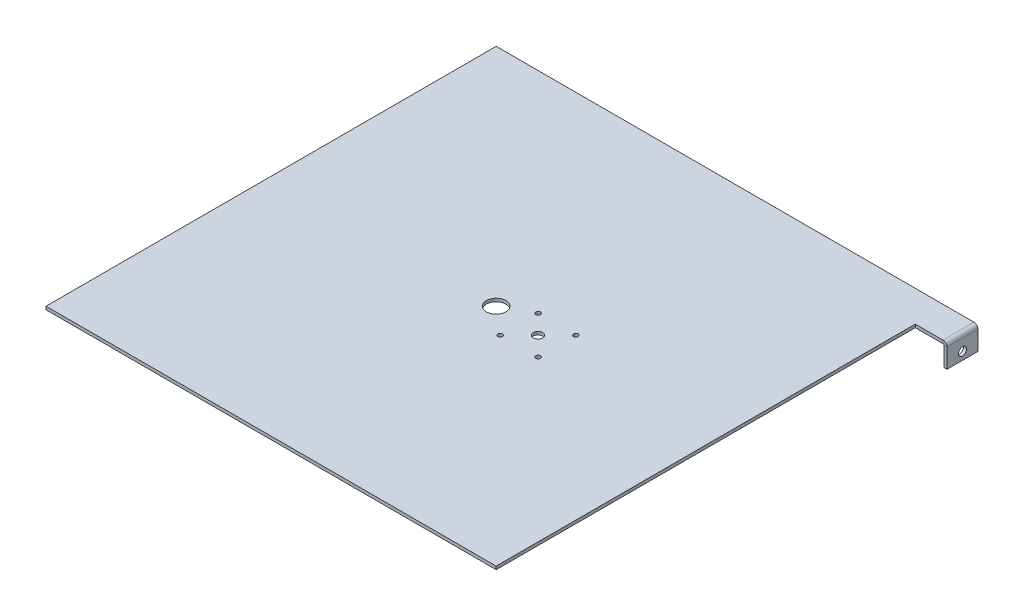
SolidWorks part; units mm, degrees
note: The reader was unsure of these and kept them because the rebuilt part matched: flange length of "Edge-Flange1".
ref_plane "Front Plane" through (0, 0, 0) normal (0, 0, 1) x (1, 0, 0)
ref_plane "Top Plane" through (0, 0, 0) normal (0, 1, 0) x (1, 0, 0)
ref_plane "Right Plane" through (0, 0, 0) normal (1, 0, 0) x (0, 0, -1)
sketch "Sketch1" plane through (0, 0, 0) normal (0, 1, 0) x (1, 0, 0)
  line L1 (0, 0) -> (368.3, 0)
  line L2 (0, 0) -> (0, 368.3)
  line L3 (0, 368.3) -> (368.3, 368.3)
  line L4 (368.3, 0) -> (368.3, 342.9)
  line L5 (368.3, 368.3) -> (394.208, 368.3)
  line L7 (368.3, 342.9) -> (394.208, 342.9)
  line L8 (394.208, 368.3) -> (394.208, 342.9)
  dimension "D1" = 368.3
  dimension "D2" = 368.3
  dimension "D3" = 25.908
  dimension "D4" = 25.4
base flange "Base-Flange1" sketch "Sketch1" thickness 2.54 reverse thickness direction no parameters "D1"=0.7366
sketch "Sketch6" plane through (0, 0, 0) normal (0, 1, 0) x (1, 0, 0)
  circle A0 centre (221.844, 180.7376) radius 3.81
  circle A1 centre (237.338, 165.2436) radius 1.905
  circle A2 centre (237.338, 196.2316) radius 1.905
  circle A3 centre (206.35, 196.2316) radius 1.905
  circle A4 centre (206.35, 165.2436) radius 1.905
  dimension "D1" = 7.62
  dimension "D2" = 3.81
  dimension "D3" = 3.81
  dimension "D4" = 3.81
  dimension "D5" = 3.81
sketch "Sketch8" plane through (0, 0, 0) normal (0, 1, 0) x (1, 0, 0)
  line L0 (381, 342.9) -> (381, 368.3)
  line L1 (368.3, 342.9) -> (394.208, 342.9) construction
  line L2 (394.208, 368.3) -> (0, 368.3) construction
  dimension "D1" = 12.7
extrude "Cut-Extrude1" cut sketch "Sketch6" against normal up to surface (2.54 mm away) normal cut yes up to face at (254.1693, -2.54, -237.0667)
sketch "Sketch7" plane through (0, -2.54, 0) normal (0, -1, 0) x (-1, 0, 0)
  line L0 (-368.3, 0) -> (-368.3, 342.9) construction
  line L1 (-394.208, 368.3) -> (0, 368.3) construction
  circle A0 centre (-184.15, 184.15) radius 8
  dimension "D1" = 16
  dimension "D2" = 184.15
  dimension "D3" = 184.15
extrude "Cut-Extrude2" cut sketch "Sketch7" against normal blind 2.54 normal cut yes
edge flange "Edge-Flange1" sketch "Sketch11" flange angle 90 flange length 19.05 flange position material inside bend radius 0.7366 thickness 2.54 relief rectangular parameters "D6"=10
sketch "Sketch11" plane through (394.208, -2.54, 0) normal (-1, 0, 0) x (0, 0, -1)
  line L2 (342.9, 0) -> (342.9, 16.51)
  line L3 (342.9, 16.51) -> (368.3, 16.51)
  line L4 (368.3, 16.51) -> (368.3, 0)
  line L9 (368.3, 0) -> (342.9, 0) construction
  line L10 (368.3, 0) -> (342.9, 0)
bend "EdgeBend1" bend radius 0.7366 bend angle 90 parameters "D5"=1
sketch "Sketch12" plane through (394.208, 0, 0) normal (1, 0, 0) x (0, 0, -1)
  line L0 (368.3, -3.2766) -> (368.3, -19.05) construction
  line L1 (368.3, -19.05) -> (342.9, -19.05) construction
  circle A0 centre (355.6, -12.7) radius 3.302
  dimension "D1" = 6.604
  dimension "D2" = 12.7
  dimension "D3" = 6.35
extrude "Cut-Extrude3" cut sketch "Sketch12" against normal blind 2.54 normal cut yes
sketch "Bend-Lines1" [suppressed] plane through (0, 0, 0) normal (0, 1, 0) x (1, 0, 0)
sketch "Bounding-Box1" [suppressed] plane through (0, 0, 0) normal (0, 1, 0) x (1, 0, 0)
sheet metal parameters "Sheet-Metal1" thickness 2.54 parameters "D1"=0.7366
flat pattern "Flat-Pattern1" [suppressed]
sketch "Bend-Lines2" plane through (381.8394, 0, 0) normal (1, 0, 0) x (0, 0, -1)
  line L0 (342.9, -0.8394) -> (368.3, -0.8394) construction
  line L1 (342.9, -0.8394) -> (368.3, -0.8394) construction
sketch3d "Bounding-Box2" [suppressed]
  line L0 (368.3, -406.4, 0) -> (368.3, 0, 0) construction
  line L1 (0, -406.4, 0) -> (0, 0, 0) construction
  line L2 (368.3, -406.4, 0) -> (0, -406.4, 0) construction
  line L3 (368.3, 0, 0) -> (0, 0, 0) construction
sheet metal parameters "Sheet-Metal2" thickness 2.54 parameters "D1"=0.7366
flat pattern "Flat-Pattern1"
sketch "Bend-Lines2" plane through (0, 0, 0) normal (0, 1, 0) x (1, 0, 0)
sketch3d "Bounding-Box2" [suppressed]
  line L0 (0, 0, 0) -> (0, 368.3, 0) construction
  line L1 (368.3, 0, 0) -> (368.3, 368.3, 0) construction
  line L2 (0, 0, 0) -> (368.3, 0, 0) construction
  line L3 (0, 368.3, 0) -> (368.3, 368.3, 0) construction
sheet metal parameters "Sheet-Metal3" thickness 2.54 parameters "D1"=0.7366
flat pattern "Flat-Pattern1"
sketch "Bend-Lines2" plane through (381.8394, 0, 0) normal (1, 0, 0) x (0, 0, -1)
sketch3d "Bounding-Box2" [suppressed]
  line L0 (406.4, 368.3, 0) -> (0, 368.3, 0) construction
  line L1 (406.4, 0, 0) -> (0, 0, 0) construction
  line L2 (406.4, 368.3, 0) -> (406.4, 0, 0) construction
  line L3 (0, 368.3, 0) -> (0, 0, 0) construction
sheet metal parameters "Sheet-Metal4" thickness 2.54 parameters "D1"=0.7366
flat pattern "Flat-Pattern1"
sketch "Bend-Lines2" plane through (0, 0, 0) normal (0, 1, 0) x (1, 0, 0)
  line L0 (379.2994, 342.9) -> (379.2994, 368.3) construction
  line L1 (379.2994, 342.9) -> (379.2994, 368.3) construction
sketch3d "Bounding-Box2" [suppressed]
  line L0 (396.6488, 368.3, 0) -> (0, 368.3, 0) construction
  line L1 (396.6488, 0, 0) -> (0, 0, 0) construction
  line L2 (396.6488, 368.3, 0) -> (396.6488, 0, 0) construction
  line L3 (0, 368.3, 0) -> (0, 0, 0) construction
bend of the flat pattern "Flatten-<EdgeBend1>1"
sheet metal parameters "Sheet-Metal5" thickness 2.54 parameters "D1"=0.7366
flat pattern "Flat-Pattern1"
sketch "Bend-Lines2" plane through (0, 0, 0) normal (0, 1, 0) x (1, 0, 0)
  line L0 (379.2994, 342.9) -> (379.2994, 368.3) construction
  line L1 (379.2994, 342.9) -> (379.2994, 368.3) construction
sketch3d "Bounding-Box2" [suppressed]
  line L0 (396.6488, 368.3, 0) -> (0, 368.3, 0) construction
  line L1 (396.6488, 0, 0) -> (0, 0, 0) construction
  line L2 (396.6488, 368.3, 0) -> (396.6488, 0, 0) construction
  line L3 (0, 368.3, 0) -> (0, 0, 0) construction
bend of the flat pattern "Flatten-<EdgeBend1>1"
